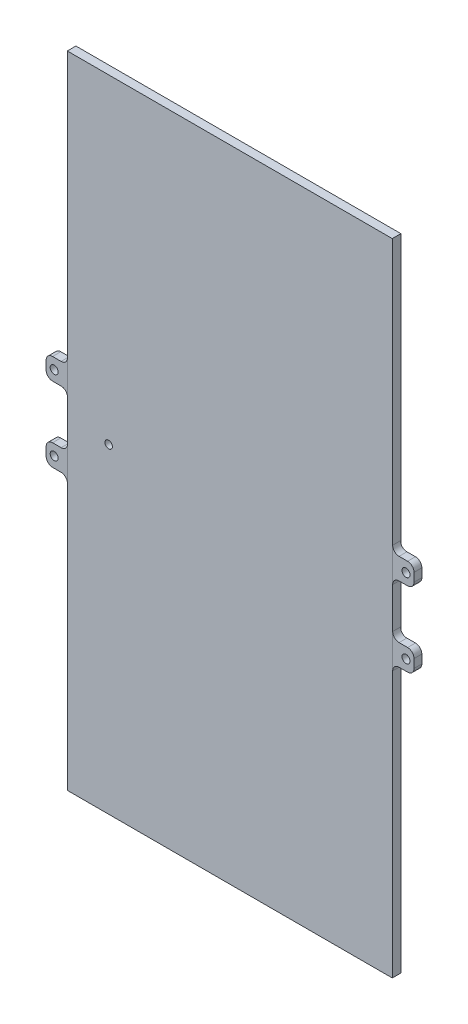
SolidWorks part; units mm, degrees
ref_plane "Front Plane" through (0, 0, 0) normal (1, 0, 0) x (0, 1, 0)
ref_plane "Top Plane" through (0, 0, 0) normal (0, 0, 1) x (0, 1, 0)
ref_plane "Right Plane" through (0, 0, 0) normal (0, 1, 0) x (-1, 0, 0)
sketch "Sketch1" plane through (0, 0, 0) normal (0, 0, 1) x (0, 1, 0)
  line L1 (-60, -30.45) -> (60, -30.45)
  line L2 (-60, -30.45) -> (-60, 30.45)
  line L3 (-60, 30.45) -> (60, 30.45)
  line L4 (60, -30.45) -> (60, 30.45)
  line L5 (-60, -30.45) -> (60, 30.45) construction
  line L6 (-60, 30.45) -> (60, -30.45) construction
  point P0 (0, 0)
  dimension "D1" = 120
  dimension "D2" = 60.9
extrude "Boss-Extrude1" add sketch "Sketch1" along normal blind 1.61
sketch "Sketch2" plane through (0, 0, 0) normal (0, 0, -1) x (1, 0, 0)
  line L1 (28.4817, 0) -> (17.4151, 6.3893)
  line L2 (17.4151, 6.3893) -> (17.4151, -6.3893)
  line L3 (17.4151, -6.3893) -> (28.4817, 0)
  circle A0 centre (21.104, 0) radius 3.6889 construction
extrude "Cut-Extrude1" cut sketch "Sketch2" against normal blind 0.5 contours L3 L1 L2
sketch "Sketch3" plane through (-30.45, 0, 0) normal (-1, 0, 0) x (0, -1, 0)
  line L0 (-60, 1.61) -> (-60, 0) construction
  line L1 (60, 0.035) -> (-60, 0.035)
  line L2 (60, 0.035) -> (60, 1.575)
  line L3 (60, 1.575) -> (-60, 1.575)
  line L4 (-60, 0.035) -> (-60, 1.575)
  line L5 (60, 0.035) -> (-60, 1.575) construction
  line L6 (60, 1.575) -> (-60, 0.035) construction
  line L7 (-60, 1.61) -> (60, 1.61) construction
  line L8 (-60, 0) -> (60, 0) construction
  line L9 (-9, 0.035) -> (-5, 0.035)
  line L10 (-9, 0.035) -> (-9, 1.575)
  line L11 (-9, 1.575) -> (-5, 1.575)
  line L12 (-5, 0.035) -> (-5, 1.575)
  line L13 (-9, 0.035) -> (-5, 1.575) construction
  line L14 (-9, 1.575) -> (-5, 0.035) construction
  line L15 (5, 0.035) -> (9, 0.035)
  line L16 (5, 0.035) -> (5, 1.575)
  line L17 (5, 1.575) -> (9, 1.575)
  line L18 (9, 0.035) -> (9, 1.575)
  line L19 (5, 0.035) -> (9, 1.575) construction
  line L20 (5, 1.575) -> (9, 0.035) construction
  point P0 (0, 0.805)
  point P9 (-7, 0.805)
  point P14 (7, 0.805)
  dimension "D1" = 0.035
  dimension "D2" = 0.035
  dimension "D3" = 4
  dimension "D4" = 4
  dimension "D5" = 5
  dimension "D6" = 5
sketch "Sketch5" plane through (30.45, 0, 0) normal (1, 0, 0) x (0, 1, 0)
  line L0 (-60, 0.035) -> (-60, 1.575) construction
  line L1 (60, 1.54) -> (-60, 1.54)
  line L2 (60, 1.54) -> (60, 0.07)
  line L3 (60, 0.07) -> (-60, 0.07)
  line L4 (-60, 1.54) -> (-60, 0.07)
  line L5 (60, 1.54) -> (-60, 0.07) construction
  line L6 (60, 0.07) -> (-60, 1.54) construction
  line L7 (-60, 0.035) -> (60, 0.035) construction
  line L9 (9, 0.07) -> (5, 0.07)
  line L10 (9, 0.07) -> (9, 1.54)
  line L11 (9, 1.54) -> (5, 1.54)
  line L12 (5, 0.07) -> (5, 1.54)
  line L13 (9, 0.07) -> (5, 1.54) construction
  line L14 (9, 1.54) -> (5, 0.07) construction
  line L15 (-9, 0.07) -> (-5, 0.07)
  line L16 (-9, 0.07) -> (-9, 1.54)
  line L17 (-9, 1.54) -> (-5, 1.54)
  line L18 (-5, 0.07) -> (-5, 1.54)
  line L19 (-9, 0.07) -> (-5, 1.54) construction
  line L20 (-9, 1.54) -> (-5, 0.07) construction
  point P0 (0, 0.805)
  point P10 (7, 0.805)
  point P15 (-7, 0.805)
  dimension "D1" = 0.035
  dimension "D2" = 4
  dimension "D3" = 4
  dimension "D4" = 5
  dimension "D5" = 5
extrude "Boss-Extrude2" add sketch "Sketch3" along normal blind 4 contours L10 L11 L12 L9 | L18 L17 L16 L15
extrude "Boss-Extrude3" add sketch "Sketch5" along normal blind 4 contours L12 L11 L10 L9 | L18 L17 L16 L15
sketch "Sketch7" plane through (0, 0, 1.54) normal (0, 0, 1) x (1, 0, 0)
  line L0 (-34.45, 9) -> (-30.45, 9) construction
  line L1 (-34.45, 9) -> (-34.45, 5) construction
  line L2 (-34.45, -9) -> (-30.45, -9) construction
  line L3 (-34.45, -5) -> (-34.45, -9) construction
  line L4 (34.45, -9) -> (30.45, -9) construction
  line L5 (34.45, -9) -> (34.45, -5) construction
  line L6 (34.45, 9) -> (30.45, 9) construction
  line L7 (34.45, 9) -> (34.45, 5) construction
  circle A0 centre (32.95, 7) radius 0.75
  circle A1 centre (32.95, -7) radius 0.75
  circle A2 centre (-32.95, -7) radius 0.75
  circle A3 centre (-32.95, 7) radius 0.75
  dimension "D1" = 1.5
  dimension "D2" = 1.5
  dimension "D3" = 1.5
  dimension "D4" = 1.5
  dimension "D8" = 1.5
  dimension "D9" = 2
  dimension "D10" = 1.5
  dimension "D11" = 2
  dimension "D12" = 1.5
  dimension "D5" = 2
  dimension "D6" = 1.5
  dimension "D7" = 2
extrude "Cut-Extrude3" cut sketch "Sketch7" against normal through all both and the other way through all contours A0 | A1 | A2 | A3
fillet "Fillet1" radius 1.2 8 edges at (30.45, 9, 0.805) (30.45, -5, 0.805) (30.45, -9, 0.805) (30.45, 5, 0.805) (-30.45, 9, 0.805) (-30.45, 5, 0.805) (-30.45, -9, 0.805) (-30.45, -5, 0.805)
fillet "Fillet2" radius 1.2 8 edges at (-34.45, -9, 0.805) (-34.45, -5, 0.805) (-34.45, 5, 0.805) (-34.45, 9, 0.805) (34.45, 9, 0.805) (34.45, 5, 0.805) (34.45, -9, 0.805) (34.45, -5, 0.805)
sketch "Sketch8" plane through (0, 0, 0) normal (0, 0, -1) x (1, 0, 0)
  line L0 (-30.45, -60) -> (-30.45, 60) construction
  circle A0 centre (-22.7, 0) radius 0.7
  dimension "D2" = 1.4
  dimension "D1" = 7.75
extrude "Cut-Extrude4" cut sketch "Sketch8" against normal through all contours A0
sketch "Sketch9" plane through (0, 0, 0.07) normal (0, 0, -1) x (-1, 0, 0)
  line L0 (-30.45, -10.2) -> (-30.45, -3.8) construction
  point P0 (-30.45, -7)
  point P1 (0, 0)
  point P4 (0, 0)
